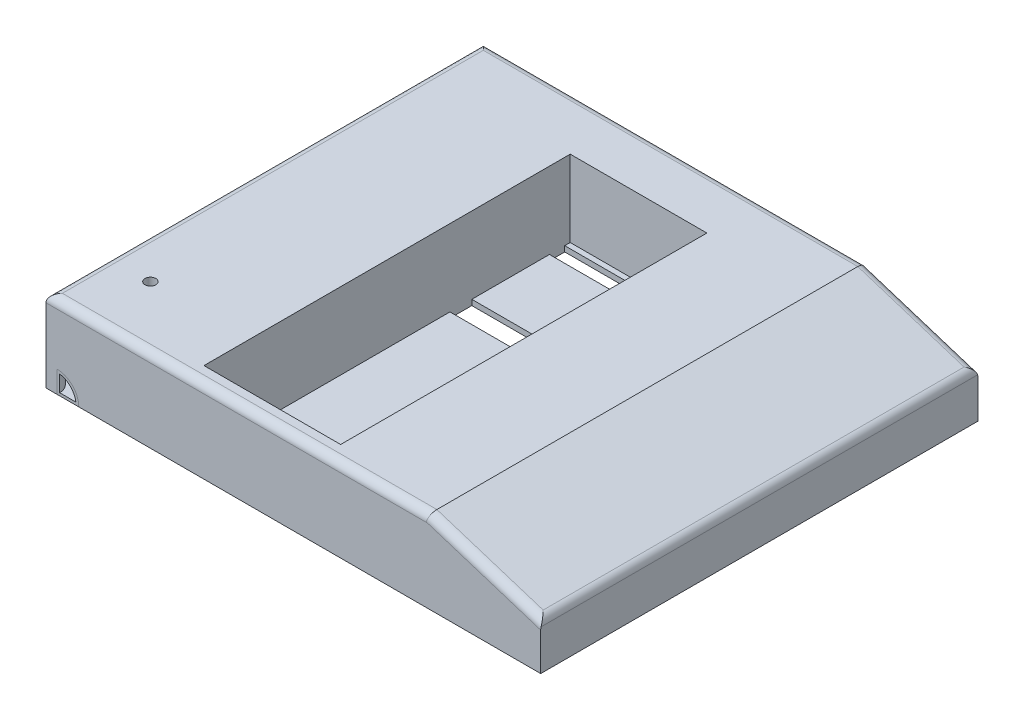
SolidWorks part; units mm, degrees
ref_plane "Front Plane" through (0, 0, 0) normal (0, 0, 1) x (1, 0, 0)
ref_plane "Top Plane" through (0, 0, 0) normal (0, 1, 0) x (1, 0, 0)
ref_plane "Right Plane" through (0, 0, 0) normal (1, 0, 0) x (0, 0, -1)
sketch3d "3DSketch2" plane through (0, 0, 0) normal (0, 0, 1) x (1, 0, 0)
sketch "Sketch1" plane through (0, 0, 0) normal (0, 1, 0) x (1, 0, 0)
  line L1 (-45.25, -40) -> (45.25, -40)
  line L2 (-45.25, -40) -> (-45.25, 40)
  line L3 (-45.25, 40) -> (45.25, 40)
  line L4 (45.25, -40) -> (45.25, 40)
  line L5 (-45.25, -40) -> (45.25, 40) construction
  line L6 (-45.25, 40) -> (45.25, -40) construction
  point P0 (0, 0)
  dimension "D1" = 80
  dimension "D2" = 90.5
extrude "Boss-Extrude1" add sketch "Sketch1" along normal blind 15
shell "Shell3" thickness 1.5 removed face at (0, 0, 0)
sketch "Sketch4" plane through (-45.25, 0, 0) normal (-1, 0, 0) x (0, 0, 1)
  line L0 (-34.3, 1.6) -> (-28.56, 1.6) construction
  line L1 (-34.3, 3.2) -> (-28.56, 3.2)
  line L2 (-34.3, 0) -> (-28.56, 0)
  arc A0 (-34.3, 3.2) -> (-34.3, 0) centre (-34.3, 1.6) ccw
  arc A1 (-28.56, 0) -> (-28.56, 3.2) centre (-28.56, 1.6) ccw
  point P2 (-31.43, 1.6)
extrude "Cut-Extrude2" cut sketch "Sketch4" against normal blind 1.5
sketch "Sketch6" plane through (-45.25, 0, 0) normal (-1, 0, 0) x (0, 0, 1)
  line L0 (-28.56, 0) -> (40, 0) construction
  line L1 (-24.15, 7.1) -> (-11, 7.1)
  line L2 (-24.15, 7.1) -> (-24.15, 0)
  line L3 (-24.15, 0) -> (-11, 0)
  line L4 (-11, 7.1) -> (-11, 0)
  line L5 (-24.15, 7.1) -> (-11, 0) construction
  line L6 (-24.15, 0) -> (-11, 7.1) construction
  line L7 (-40, 15) -> (-40, 0) construction
  dimension "D1" = 7.1
  dimension "D2" = 13.15
  dimension "D3" = 0
  dimension "D4" = 15.85
extrude "Cut-Extrude3" cut sketch "Sketch6" against normal blind 1.5
sketch "Sketch9" plane through (-45.25, 0, 0) normal (-1, 0, 0) x (0, 0, 1)
  line L0 (-28.56, 0) -> (-24.15, 0) construction
  line L1 (-25.65, 0) -> (-9.5, 0)
  line L2 (-25.65, 0) -> (-25.65, 1.55)
  line L3 (-25.65, 1.55) -> (-9.5, 1.55)
  line L4 (-9.5, 0) -> (-9.5, 1.55)
  line L5 (-11, 0) -> (-11, 7.1) construction
  dimension "D1" = 16.15
  dimension "D2" = 1.55
  dimension "D3" = 1.5
extrude "Boss-Extrude2" add sketch "Sketch9" along normal blind 1.5
sketch "Sketch11" plane through (0, 15, 0) normal (0, 1, 0) x (1, 0, 0)
  line L1 (-45.25, 40) -> (-45.25, -40) construction
  circle A0 centre (-37.55, -28.6) radius 1
  dimension "D1" = 7.7
fillet "Fillet7" radius 1.5 4 edges at (45.25, 15, 0) (0, 15, 40) (0, 15, -40) (-45.25, 15, 0)
sketch "Sketch20" plane through (0, 15, 0) normal (0, 1, 0) x (1, 0, 0)
  line L0 (-45.25, 40) -> (45.25, 40) construction
  line L1 (5.65, 30) -> (-19.35, 30)
  line L2 (5.65, 30) -> (5.65, -37)
  line L3 (5.65, -37) -> (-19.35, -37)
  line L4 (-19.35, 30) -> (-19.35, -37)
  line L5 (45.25, -40) -> (-45.25, -40) construction
  line L6 (-43.75, 38.5) -> (-43.75, -38.5) construction
  dimension "D1" = 10
  dimension "D2" = 3
  dimension "D3" = 24.4
  dimension "D4" = 25
extrude "Boss-Extrude8" add sketch "Sketch20" against normal blind 14
extrude "Cut-Extrude9" cut sketch "Sketch20<2>" against normal blind 1.5
sketch "Sketch20<2>" plane through (0, 15, 0) normal (0, 1, 0) x (1, 0, 0) same geometry as "Sketch20"
shell "Shell6" thickness 1 removed face at (-6.85, 13.5, 3.5) outward yes
sketch "Sketch21" plane through (0, 13.5, 0) normal (0, -1, 0) x (-1, 0, 0)
  line L0 (43.75, -38.5) -> (-43.75, -38.5) construction
  line L1 (-6.65, -38) -> (-5.65, -38)
  line L2 (-6.65, -38) -> (-6.65, -38.5)
  line L3 (-6.65, -38.5) -> (-5.65, -38.5)
  line L4 (-5.65, -38) -> (-5.65, -38.5)
  line L5 (-43.75, 38.5) -> (43.75, 38.5) construction
  line L6 (-6.65, 31) -> (-5.65, 31)
  line L7 (-6.65, 31) -> (-6.65, 38.5)
  line L8 (-6.65, 38.5) -> (-5.65, 38.5)
  line L9 (-5.65, 31) -> (-5.65, 38.5)
  dimension "D1" = 1
  dimension "D2" = 1
extrude "Boss-Extrude9" add sketch "Sketch21" along normal blind 13.5
extrude "Boss-Extrude10" add sketch "Sketch11" against normal blind 10
extrude "Cut-Extrude10" cut sketch "Sketch11<3>" against normal blind 1.5
sketch "Sketch11<3>" plane through (0, 15, 0) normal (0, 1, 0) x (1, 0, 0) same geometry as "Sketch11"
shell "Shell9" thickness 1 removed face at (-37.55, 5, 29.6) removed face at (-37.55, 13.5, 29.6) outward yes
sketch "Sketch33" plane through (0, 0, 40) normal (0, 0, 1) x (1, 0, 0)
  line L3 (-45.25, 0) -> (45.25, 0) construction
  line L6 (-43.25, 4) -> (-43.25, 0)
  line L7 (-43.25, 0) -> (-39.25, 0)
  arc A2 (-43.25, 4) -> (-39.25, 0) centre (-43.25, 0) cw
  dimension "D1" = 2
revolve "Cut-Revolve4" cut sketch "Sketch33" angle 90 about axis through (-45.25, 15, 40) along (0, -1, 0) reverse direction yes
revolve "Revolve3" add sketch "Sketch33<2>" angle 90 about axis through (-45.25, 15, 40) along (0, -1, 0) reverse direction yes
sketch "Sketch33<2>" plane through (0, 0, 40) normal (0, 0, 1) x (1, 0, 0) same geometry as "Sketch33"
shell "Shell14" thickness 0.5 removed face at (-45.25, 1.6095, 36.3905) removed face at (-41.6405, 1.6095, 40)
sketch "Sketch41" plane through (0, 1, 0) normal (0, 1, 0) x (1, 0, 0)
  line L0 (5.65, -37) -> (5.65, 30) construction
  line L1 (5.65, 29) -> (-19.35, 29)
  line L2 (5.65, 29) -> (5.65, 26.2)
  line L3 (5.65, 26.2) -> (-19.35, 26.2)
  line L4 (-19.35, 29) -> (-19.35, 26.2)
  line L5 (-19.35, 30) -> (-19.35, -37) construction
  line L6 (-45.25, 40) -> (45.25, 40) construction
  line L7 (5.65, 12) -> (-19.35, 12)
  line L8 (5.65, 12) -> (5.65, 8)
  line L9 (5.65, 8) -> (-19.35, 8)
  line L10 (-19.35, 12) -> (-19.35, 8)
  line L11 (5.65, -26.3) -> (-19.35, -26.3)
  line L12 (5.65, -26.3) -> (5.65, -28.7)
  line L13 (5.65, -28.7) -> (-19.35, -28.7)
  line L14 (-19.35, -26.3) -> (-19.35, -28.7)
  line L15 (-39.25, -40) -> (45.25, -40) construction
  dimension "D1" = 11
  dimension "D2" = 13.8
  dimension "D3" = 28
  dimension "D4" = 32
  dimension "D5" = 13.7
  dimension "D6" = 11.3
extrude "Cut-Extrude11" cut sketch "Sketch41" against normal up to next (1 mm away)
sketch "Sketch45" plane through (6.626, 20.7816, 0) normal (-0.3038, -0.9527, 0) x (-0.9527, 0.3038, 0)
  line L5 (-40.5397, -40) -> (-19.0325, -40)
  line L6 (-40.5397, -40) -> (-40.5397, 40)
  line L7 (-40.5397, 40) -> (-19.0325, 40)
  line L8 (-19.0325, -40) -> (-19.0325, 40)
extrude "Cut-Extrude13" cut sketch "Sketch45" against normal blind 10
extrude "Boss-Extrude11" add sketch "Sketch45<2>" along normal blind 1.5
sketch "Sketch45<2>" plane through (6.626, 20.7816, 0) normal (-0.3038, -0.9527, 0) x (-0.9527, 0.3038, 0) same geometry as "Sketch45"
fillet "Fillet11" radius 1.5 3 edges at (45.25, 8.4667, 0) (35.0045, 11.7333, 40) (35.0045, 11.7333, -40)
